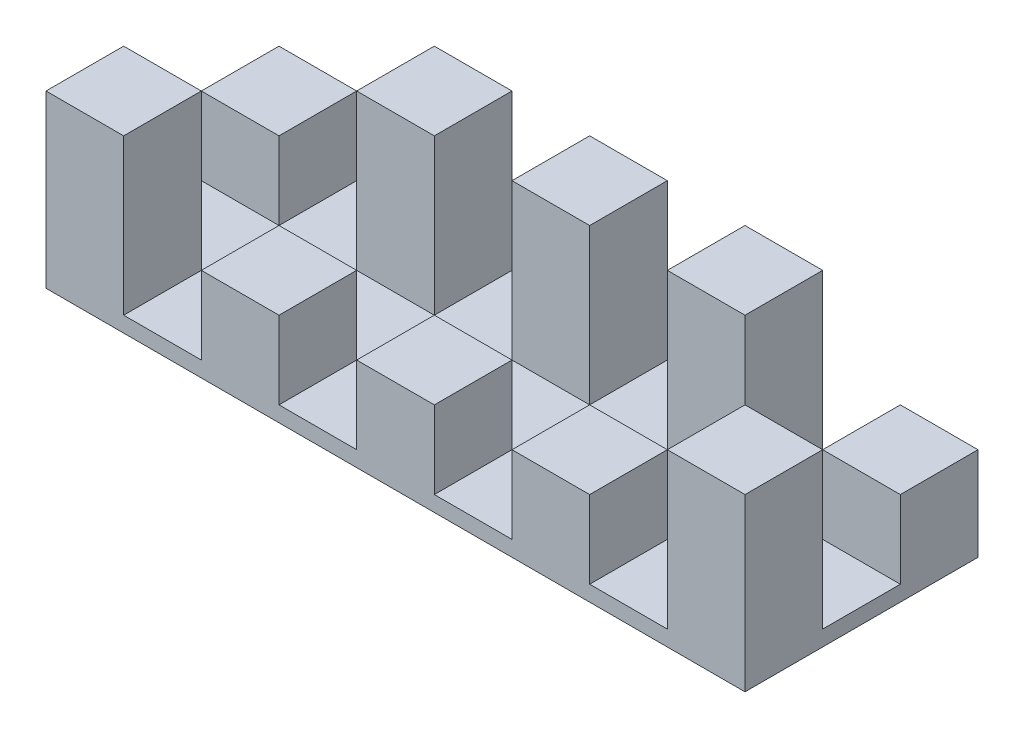
SolidWorks part; units mm, degrees
ref_plane "Front Plane" through (0, 0, 0) normal (0, 0, 1) x (1, 0, 0)
ref_plane "Top Plane" through (0, 0, 0) normal (0, 1, 0) x (1, 0, 0)
ref_plane "Right Plane" through (0, 0, 0) normal (1, 0, 0) x (0, 0, -1)
sketch "Sketch1" plane through (0, 0, 0) normal (0, 1, 0) x (1, 0, 0)
  line L46 (0, 0) -> (11430, 0)
  line L47 (0, 0) -> (0, 3810)
  line L48 (0, 3810) -> (11430, 3810)
  line L49 (11430, 0) -> (11430, 3810)
  dimension "D1" = 3810
  dimension "D2" = 11430
extrude "Boss-Extrude2" add sketch "Sketch1" along normal blind 254
sketch "Sketch2" plane through (0, 254, 0) normal (0, 1, 0) x (1, 0, 0)
  line L0 (2540, 1270) -> (3810, 1270)
  line L1 (0, 1270) -> (1270, 1270)
  line L2 (0, 1270) -> (0, 0)
  line L3 (0, 0) -> (1270, 0)
  line L4 (1270, 1270) -> (1270, 0)
  line L5 (2540, 1270) -> (2540, 0)
  line L6 (2540, 0) -> (3810, 0)
  line L7 (3810, 1270) -> (3810, 0)
  line L8 (5080, 1270) -> (6350, 1270)
  line L9 (5080, 1270) -> (5080, 0)
  line L10 (5080, 0) -> (6350, 0)
  line L11 (6350, 1270) -> (6350, 0)
  line L12 (7620, 1270) -> (8890, 1270)
  line L13 (7620, 1270) -> (7620, 0)
  line L14 (7620, 0) -> (8890, 0)
  line L15 (8890, 1270) -> (8890, 0)
  line L16 (10160, 1270) -> (11430, 1270)
  line L17 (10160, 1270) -> (10160, 0)
  line L18 (10160, 0) -> (11430, 0)
  line L19 (11430, 1270) -> (11430, 0)
  line L20 (2540, 3810) -> (3810, 3810)
  line L21 (2540, 3810) -> (2540, 2540)
  line L22 (2540, 2540) -> (3810, 2540)
  line L23 (3810, 3810) -> (3810, 2540)
  line L24 (5080, 3810) -> (6350, 3810)
  line L25 (5080, 3810) -> (5080, 2540)
  line L26 (5080, 2540) -> (6350, 2540)
  line L27 (6350, 3810) -> (6350, 2540)
  line L28 (7620, 3810) -> (8890, 3810)
  line L29 (7620, 3810) -> (7620, 2540)
  line L30 (7620, 2540) -> (8890, 2540)
  line L31 (8890, 3810) -> (8890, 2540)
  line L32 (10160, 3810) -> (11430, 3810)
  line L33 (10160, 3810) -> (10160, 2540)
  line L34 (10160, 2540) -> (11430, 2540)
  line L35 (11430, 3810) -> (11430, 2540)
  line L36 (0, 3810) -> (1270, 3810)
  line L37 (0, 3810) -> (0, 2540)
  line L38 (0, 2540) -> (1270, 2540)
  line L39 (1270, 3810) -> (1270, 2540)
  line L40 (0, 3810) -> (0, 0) construction
  line M41 (0, 3810) -> (0, 0)
  line M42 (0, 0) -> (11430, 0)
  line M43 (11430, 0) -> (11430, 3810)
  line M44 (11430, 3810) -> (0, 3810)
  dimension "D1" = 1270
  dimension "D4" = 1270
  dimension "D5" = 1270
  dimension "D2" = 5
  dimension "D3" = 2
extrude "Boss-Extrude6" add sketch "Sketch2" along normal blind 1270 contours L39 L38 M44 M41 | L7 L0 L5 M42 | L11 L8 L9 M42 | L15 L12 L13 M42 | L33 L34 M43 M44 region at (3175, 254, -635) region at (5715, 254, -635) region at (8255, 254, -635) region at (635, 254, -3175) region at (10795, 254, -3175)
extrude "Boss-Extrude7" add sketch "Sketch2<5>" along normal blind 2540 contours L4 L1 M41 M42 | L23 L21 L22 M44 | L27 L25 L26 M44 | L31 L29 L30 M44 | L16 L17 M42 M43 region at (635, 254, -635) region at (10795, 254, -635) region at (3175, 254, -3175) region at (5715, 254, -3175) region at (8255, 254, -3175)
sketch "Sketch2<5>" plane through (0, 254, 0) normal (0, 1, 0) x (1, 0, 0) same geometry as "Sketch2"
